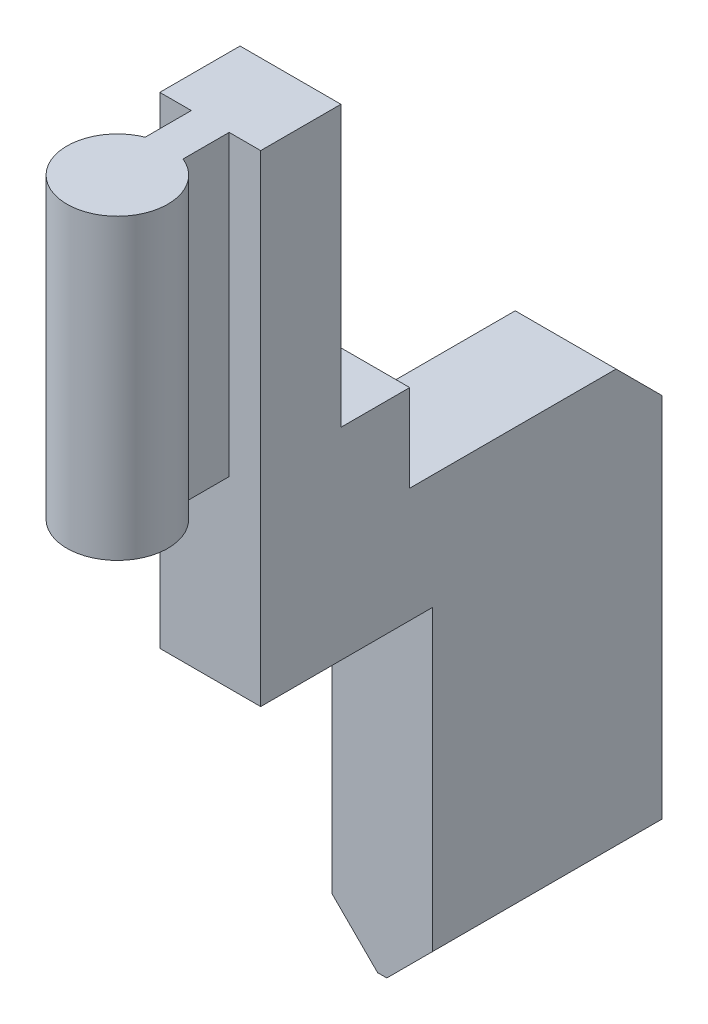
SolidWorks part; units mm, degrees
ref_plane "Płaszczyzna przednia" through (0, 0, 0) normal (0, 0, 1) x (1, 0, 0)
ref_plane "Płaszczyzna górna" through (0, 0, 0) normal (0, 1, 0) x (1, 0, 0)
ref_plane "Płaszczyzna prawa" through (0, 0, 0) normal (1, 0, 0) x (0, 0, -1)
sketch "Szkic1" plane through (0, 0, 0) normal (0, 0, 1) x (1, 0, 0)
  line L1 (-2.2, 10.5) -> (2.2, 10.5)
  line L2 (-2.2, 10.5) -> (-2.2, -10.5)
  line L3 (-2.2, -10.5) -> (2.2, -10.5)
  line L4 (2.2, 10.5) -> (2.2, -10.5)
  line L5 (-2.2, 10.5) -> (2.2, -10.5) construction
  line L6 (-2.2, -10.5) -> (2.2, 10.5) construction
  point P0 (0, 0)
  dimension "D1" = 4.4
  dimension "D2" = 21
extrude "Dodanie-wyciągnięcie1" add sketch "Szkic1" along normal blind 6.5
sketch "Szkic3" plane through (0, 10.5, 0) normal (0, 1, 0) x (1, 0, 0)
  line L0 (0, -6.5) -> (0, -10.55) construction
  line L1 (2.2, -6.5) -> (-2.2, -6.5) construction
  line L3 (0.825, -6.5) -> (0.825, -10.55)
  line L4 (0.825, -6.5) -> (-0.825, -6.5)
  line L5 (-0.825, -6.5) -> (-0.825, -10.55)
  line L6 (0.825, -10.55) -> (-0.825, -10.55)
  line L7 (0.825, -6.5) -> (-0.825, -10.55) construction
  line L8 (-0.825, -6.5) -> (0.825, -10.55) construction
  circle A0 centre (0, -10.55) radius 2.2
  point P5 (0, -8.525)
  line M10 (-2.2, 0) -> (-2.2, -6.5)
  dimension "D2" = 4.4
  dimension "D1" = 4.05
  dimension "D3" = 1.65
extrude "Dodanie-wyciągnięcie2" add sketch "Szkic3" against normal blind 13 contours L5 A0 L3 L6 | L3 A0 L5 L6 | A0 L3 L5 M10 region at (0, 10.5, 7.4519) region at (0, 10.5, 10.8763) region at (0, 10.5, 9.4758)
sketch "Sketch1" plane through (0, 0, 0) normal (0, 0, -1) x (-1, 0, 0)
  line L0 (-2.2, -10.5) -> (-2.2, 10.5) construction
  line L1 (-2.2, -5.5) -> (2.2, -5.5)
  line L2 (-2.2, -5.5) -> (-2.2, -10.5)
  line L3 (-2.2, -10.5) -> (2.2, -10.5)
  line L4 (2.2, -5.5) -> (2.2, -10.5)
  line L5 (0, -10.5) -> (0, -5.5) construction
  line L6 (-2.2, -8) -> (2.2, -8) construction
  line L7 (2.2, 10.5) -> (2.2, -10.5) construction
  line L9 (2.2, -10.5) -> (-2.2, -10.5) construction
  point P460 (0, -8)
  dimension "D1" = 5
extrude "Boss-Extrude1" add sketch "Sketch1" along normal blind 11
sketch "Sketch3" plane through (0, -10.5, 0) normal (0, -1, 0) x (1, 0, 0)
  line L0 (2.2, -11) -> (-2.2, -11) construction
  line L1 (2.2, -11) -> (-2.2, -11)
  line L2 (2.2, -11) -> (2.2, -1)
  line L3 (2.2, -1) -> (-2.2, -1)
  line L4 (-2.2, -11) -> (-2.2, -1)
  line L5 (0, -1) -> (0, -11) construction
  line L6 (2.2, -6) -> (-2.2, -6) construction
  line L7 (2.2, 6.5) -> (2.2, -11) construction
  line L8 (-2.2, 6.5) -> (-2.2, -11) construction
  point P448 (0, -6)
  dimension "D2" = 10
extrude "Boss-Extrude3" add sketch "Sketch3" along normal blind 15
chamfer "Chamfer1" distance 2 angle 45 3 edges at (2.2, -25.5, -6) (-2.2, -25.5, -6) (0, -5.5, -11)
sketch "Sketch5" plane through (0, 10.5, 0) normal (0, 1, 0) x (1, 0, 0)
  line L0 (2.2, -6.5) -> (2.2, 0) construction
  line L1 (-2.2, 0) -> (2.2, 0)
  line L2 (-2.2, 0) -> (-2.2, -3)
  line L3 (-2.2, -3) -> (2.2, -3)
  line L4 (2.2, 0) -> (2.2, -3)
  line L5 (0, -3) -> (0, 0) construction
  line L6 (-2.2, -1.5) -> (2.2, -1.5) construction
  point P212 (0, -1.5)
  dimension "D1" = 3
extrude "Cut-Extrude1" cut sketch "Sketch5" against normal blind 12.2
